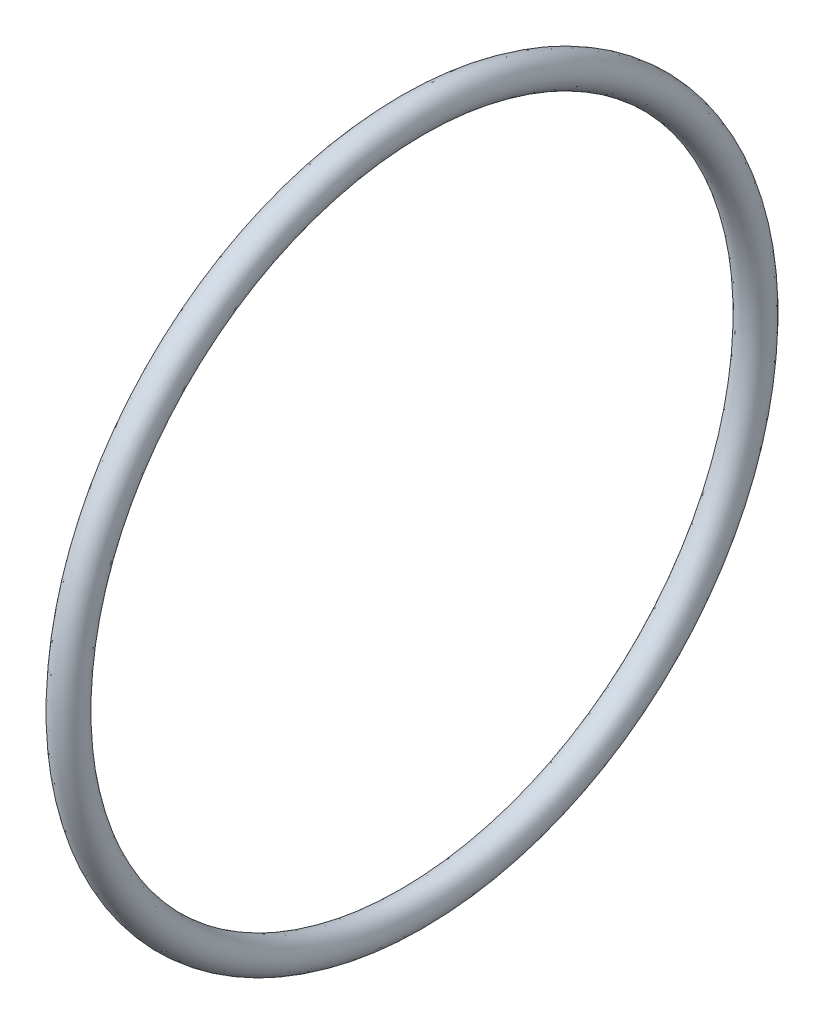
SolidWorks part; units mm, degrees
material "Rubber"
ref_plane "Front Plane" through (0, 0, 0) normal (0, 0, 1) x (1, 0, 0)
ref_plane "Top Plane" through (0, 0, 0) normal (0, 1, 0) x (1, 0, 0)
ref_plane "Right Plane" through (0, 0, 0) normal (1, 0, 0) x (0, 0, -1)
sketch "Sketch3" plane through (0, 0, 0) normal (0, 0, 1) x (1, 0, 0)
  line L0 (0, 0) -> (-7.1671, 0) construction
  ellipse E0 centre (0, 38.1381) end of major axis (0, 39.9034) minor radius 1.7653
  dimension "D1" = 3.5306
  dimension "D2" = 3.5306
  dimension "D3" = 36.3728
revolve "Revolve1" add sketch "Sketch3" angle 360 about L0
ref_axis "Axis1" through (0, 0, 0) along (-1, 0, 0)
